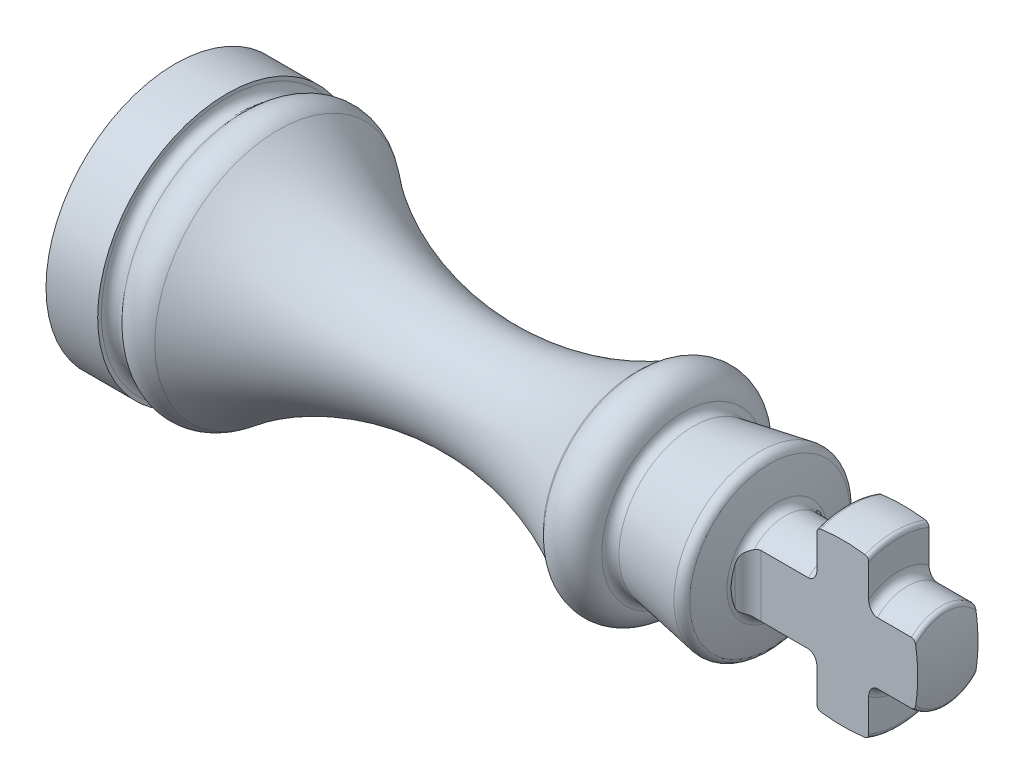
SolidWorks part; units mm, degrees
material "6061-T6 (SS)"
ref_plane "Front" through (0, 0, 0) normal (0, 0, 1) x (1, 0, 0)
ref_plane "Top" through (0, 0, 0) normal (0, 1, 0) x (1, 0, 0)
ref_plane "Right" through (0, 0, 0) normal (1, 0, 0) x (0, 0, -1)
sketch "Sketch1" plane through (0, 0, 0) normal (0, 0, 1) x (1, 0, 0)
  line L0 (0, 0) -> (0, -7.5)
  line L1 (0, -7.5) -> (3, -7.5)
  line L2 (0, 0) -> (-8.1317, 0) construction
  line L3 (0, 0) -> (45, 0)
  line L4 (3, -7.5) -> (3, -7.2856)
  line L6 (3.883, -6.9642) -> (1.6828, -4.3421) construction
  line L7 (30.064, -4.3086) -> (33.9421, -4.9924)
  line L8 (26.8509, -5.4642) -> (20.4239, 2.1952) construction
  line L9 (44.4868, -2.5) -> (42.5, -2.5)
  line L10 (42, -3) -> (42, -4.6695)
  line L11 (39, -4.6695) -> (39, -3)
  line L12 (38.5, -2.5) -> (35.4215, -2.5)
  line L13 (30.064, -4.3086) -> (29.4705, -4.2039) construction
  arc A0 (3, -7.2856) -> (3.883, -6.9642) centre (3.5, -7.2856) cw
  arc A1 (3.883, -6.9642) -> (5.9794, -7.163) centre (5.0321, -6) ccw
  arc A3 (26.8509, -5.4642) -> (29.4829, -4.7258) centre (28, -4.5) ccw
  arc A5 (30.064, -4.3086) -> (29.4829, -4.7258) centre (29.9772, -4.801) ccw
  arc A6 (5.9794, -7.163) -> (26.7116, -5.349) centre (17.6819, -21.5299) cw
  arc A7 (26.7116, -5.349) -> (26.8509, -5.4642) centre (26.4679, -5.7856) cw
  arc A8 (45, 0) -> (44.7301, -2.3077) centre (35, 0) cw
  arc A9 (39.2179, -4.9175) -> (41.7821, -4.9175) centre (40.5, 5) ccw
  arc A10 (34.9298, -2.9091) -> (34.5074, -4.6452) centre (19.1965, 0) cw
  arc A11 (33.9421, -4.9924) -> (34.5074, -4.6452) centre (34.0289, -4.5) ccw
  arc A12 (35.4215, -2.5) -> (34.9298, -2.9091) centre (35.4215, -3) ccw
  arc A13 (39, -3) -> (38.5, -2.5) centre (38.5, -3) ccw
  arc A14 (42.5, -2.5) -> (42, -3) centre (42.5, -3) ccw
  arc A15 (42, -4.6695) -> (41.7821, -4.9175) centre (41.75, -4.6695) cw
  arc A16 (39, -4.6695) -> (39.2179, -4.9175) centre (39.25, -4.6695) ccw
  arc A17 (44.7301, -2.3077) -> (44.4868, -2.5) centre (44.4868, -2.25) cw
  arc A18 (29.4829, -4.7258) -> (29.4705, -4.2039) centre (28, -4.5) ccw construction
  point P35 (42, -4.8869)
  point P38 (39, -4.8869)
  point P46 (35, -2.5)
  point P49 (39, -2.5)
  dimension "D2" = 6
  dimension "D6" = 5
  dimension "D7" = 1.5
  dimension "D4" = 0.5
  dimension "D8" = 40
  dimension "D10" = 1.5
  dimension "D11" = 3
  dimension "D9" = 12
  dimension "D12" = 10
  dimension "D14" = 10
  dimension "D15" = 10
  dimension "D16" = 0.5
  dimension "D19" = 10
  dimension "D20" = 16
  dimension "D21" = 17
  dimension "D22" = 0.25
  dimension "D1" = 15
  dimension "D3" = 45
  dimension "D5" = 3
  dimension "D13" = 3
  dimension "D17" = 20
  dimension "D18" = 4
revolve "Revolve1" add sketch "Sketch1" angle 360 about L2
sketch "Sketch3" plane through (0, 0, 0) normal (0, 0, 1) x (1, 0, 0)
  line L1 (35.4215, -2.5) -> (38.5, -2.5) construction
  line L2 (36.7361, -2.5) -> (39.2179, -2.5)
  line L3 (35.4215, -2.5) -> (38.5, -2.5) construction
  line L4 (39.2179, -2.5) -> (39.2179, -4.9175)
  line L5 (0, 0) -> (10.8163, 0) construction
  line L6 (37.1191, -2.6786) -> (38.9679, -4.8819)
  line L7 (39.2179, 4.9175) -> (39.2179, -4.9175) construction
  line L8 (36.6432, -8.767) -> (36.6432, -2.8969) construction
  line L9 (35.9212, -2.6692) -> (33.1437, -6.6359) construction
  arc A0 (37.1191, -2.6786) -> (36.7361, -2.5) centre (36.7361, -3) ccw
  arc A1 (35.4215, -2.5) -> (34.9298, -2.9091) centre (35.4215, -3) ccw construction
  arc A2 (39.2179, -4.9175) -> (41.7821, -4.9175) centre (40.5, 5) ccw construction
  arc A3 (38.9679, -4.8819) -> (39.2179, -4.9175) centre (40.5, 5) ccw
  arc A4 (36.6432, -2.8969) -> (35.9212, -2.6692) centre (36.2463, -2.8969) ccw construction
  arc A5 (33.9421, -4.9924) -> (34.5074, -4.6452) centre (34.0289, -4.5) ccw construction
  dimension "D4" = 0.3969
  dimension "D1" = 0.25
  dimension "D2" = 40
  dimension "D3" = 35
revolve "Revolve2" [suppressed] add sketch "Sketch3" angle 360 about L5
sketch "Sketch2" plane through (0, 0, 0) normal (0, 1, 0) x (1, 0, 0)
  line L0 (0, 0) -> (23.1303, 0) construction
  line L1 (45, -6) -> (35, -6)
  line L2 (45, -6) -> (45, -1.75)
  line L3 (45, -1.75) -> (35.762, -1.75)
  line L4 (35, -6) -> (35, -2.512)
  line L5 (0, 7.5) -> (0, -7.5) construction
  line L6 (35, 6) -> (35, 2.512)
  line L7 (45, 1.75) -> (35.762, 1.75)
  line L8 (45, 6) -> (45, 1.75)
  line L9 (45, 6) -> (35, 6)
  arc A0 (35, 2.512) -> (35.762, 1.75) centre (35.762, 2.512) ccw
  arc A1 (44.7301, -2.3077) -> (44.7301, 2.3077) centre (35, 0) ccw construction
  arc A2 (35.762, -1.75) -> (35, -2.512) centre (35.762, -2.512) ccw
  arc A3 (26.8509, -5.4642) -> (29.4829, -4.7258) centre (28, -4.5) ccw construction
  point P17 (35, 1.75)
  point P23 (35, -1.75)
  dimension "D3" = 0.762
  dimension "D1" = 3.5
  dimension "D2" = 10
extrude "Cut-Extrude1" cut sketch "Sketch2" against normal through all both and the other way through all
sketch "Sketch4" [suppressed] plane through (0, 0, 0) normal (1, 0, 0) x (0, 0, -1)
  line L0 (11.4963, 6.6374) -> (0, 0) construction
  line L1 (0, 0) -> (-10.8772, 6.28) construction
  line L2 (0, 0) -> (0, 8.4377) construction
  line L3 (12.7332, 7.9288) -> (0, 0.5774)
  line L4 (0, 0.5774) -> (-12.7332, 7.9288)
  line L5 (-6.2765, 13.6237) -> (0, 10)
  line L6 (0, 10) -> (6.2765, 13.6237)
  circle A1 centre (0, 0) radius 10 construction
  arc A2 (12.7332, 7.9288) -> (6.2765, 13.6237) centre (0, 0) ccw
  arc A3 (-6.2765, 13.6237) -> (-12.7332, 7.9288) centre (0, 0) ccw
  dimension "D1" = 30
  dimension "D2" = 20
  dimension "D3" = 120
  dimension "D4" = 1
extrude "Boss-Extrude1" [suppressed] add sketch "Sketch4" along normal blind 18 from offset 2 separate body
combine bodies "Combine1" [suppressed] operation type add bodies to combine 113 112
pattern_circular "CirPattern1" [suppressed] count 3 over 360 of bodies 114
